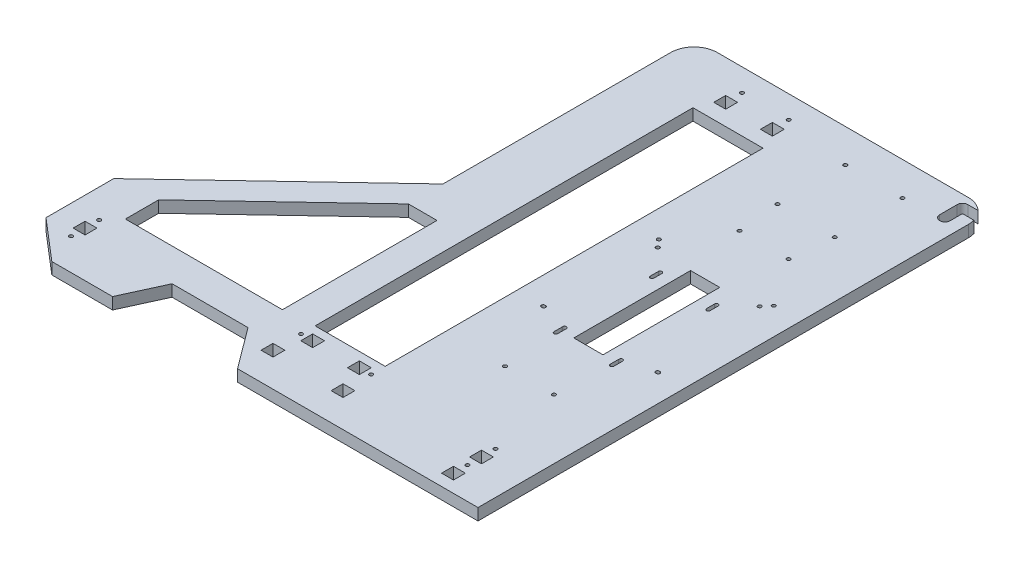
SolidWorks part; units mm, degrees
ref_plane "Front Plane" through (0, 0, 0) normal (0, 0, 1) x (1, 0, 0)
ref_plane "Top Plane" through (0, 0, 0) normal (0, 1, 0) x (1, 0, 0)
ref_plane "Right Plane" through (0, 0, 0) normal (1, 0, 0) x (0, 0, -1)
sketch "Sketch1" plane through (0, 0, 0) normal (0, 1, 0) x (1, 0, 0)
  line L0 (0, 0) -> (-235, 0)
  line L1 (-235, 0) -> (-235, -215)
  line L2 (-235, -215) -> (-380, -352)
  line L3 (-380, -352) -> (-380, -410)
  line L4 (-380, -410) -> (-345, -440)
  line L5 (-345, -440) -> (-293, -440)
  line L6 (-293, -440) -> (-277, -405)
  line L7 (-277, -405) -> (-212, -405)
  line L8 (-212, -405) -> (-185.9255, -440)
  line L9 (-185.9255, -440) -> (0, -440)
  line L10 (0, 0) -> (0, -440)
  line L12 (-293, -440) -> (-185.9255, -440) construction
  dimension "D3" = 235
  dimension "D5" = 58
  dimension "D13" = 190
  dimension "D7" = 35
  dimension "D2" = 126.686
  dimension "D11" = 65
  dimension "D15" = 52
  dimension "D12" = 30
  dimension "D10" = 35
  dimension "D14" = 16
  dimension "D6" = 380
  dimension "D4" = 440
extrude "Boss-Extrude1" add sketch "Sketch1" along normal blind 10
sketch "Sketch16" plane through (0, 10, 0) normal (0, 1, 0) x (1, 0, 0)
  line L0 (0, -440) -> (20, -440)
  line L1 (20, -440) -> (20, 0)
  line L2 (20, 0) -> (0, 0)
  line L3 (0, 0) -> (0, -440)
  dimension "D1" = 20
  dimension "D2" = 90
extrude "Boss-Extrude2" add sketch "Sketch16" against normal through all
sketch "Sketch2" plane through (0, 10, 0) normal (0, 1, 0) x (1, 0, 0)
  line L0 (-235, -215) -> (-235, -405) construction
  line L1 (-277, -405) -> (-212, -405) construction
  line L2 (-345, -440) -> (-345, -318.931) construction
  line L3 (-235, -215) -> (-380, -352) construction
  line L4 (-345, -348.5097) -> (-235, -244.5787)
  line L5 (-235, -244.5787) -> (-210.5, -244.5787)
  line L6 (-210.5, -244.5787) -> (-210.5, -377)
  line L7 (-210.5, -377) -> (-345, -377)
  line L8 (-345, -377) -> (-345, -348.5097)
  line L9 (0, -440) -> (0, 0) construction
  line L10 (-184.5, -375) -> (-124.5, -375)
  line L11 (-184.5, -375) -> (-184.5, -51.35)
  line L12 (-184.5, -51.35) -> (-124.5, -51.35)
  line L13 (-124.5, -375) -> (-124.5, -51.35)
  line L14 (-124.5, -387.1) -> (-184.5, -387.1) construction
  line L15 (-16, -440) -> (-16, 0) construction
  line L16 (20, 0) -> (-235, 0) construction
  line L17 (-355.55, -430.9571) -> (-355.55, -328.899) construction
  line L18 (-21.1, -430.1) -> (-10.9, -430.1)
  line L19 (-21.1, -430.1) -> (-21.1, -419.9)
  line L20 (-21.1, -419.9) -> (-10.9, -419.9)
  line L21 (-10.9, -430.1) -> (-10.9, -419.9)
  line L22 (-21.1, -430.1) -> (-10.9, -419.9) construction
  line L23 (-21.1, -419.9) -> (-10.9, -430.1) construction
  line L24 (-21.1, -406.1) -> (-10.9, -406.1)
  line L25 (-21.1, -406.1) -> (-21.1, -395.9)
  line L26 (-21.1, -395.9) -> (-10.9, -395.9)
  line L27 (-10.9, -406.1) -> (-10.9, -395.9)
  line L28 (-21.1, -406.1) -> (-10.9, -395.9) construction
  line L29 (-21.1, -395.9) -> (-10.9, -406.1) construction
  line L30 (-380, -410) -> (-345, -440) construction
  line L32 (-350.45, -395.9) -> (-360.65, -395.9)
  line L33 (-350.45, -395.9) -> (-350.45, -406.1)
  line L34 (-350.45, -406.1) -> (-360.65, -406.1)
  line L35 (-360.65, -395.9) -> (-360.65, -406.1)
  line L36 (-350.45, -395.9) -> (-360.65, -406.1) construction
  line L37 (-350.45, -406.1) -> (-360.65, -395.9) construction
  line L38 (-185.9255, -440) -> (20, -440) construction
  line L39 (-185.9255, -440) -> (20, -440) construction
  line L40 (-173.924, -33.35) -> (-113.924, -33.35) construction
  line L41 (-154.5, -51.35) -> (-154.5, -33.35) construction
  line L42 (-179.6, -28.25) -> (-169.4, -28.25)
  line L43 (-179.6, -28.25) -> (-179.6, -38.45)
  line L44 (-179.6, -38.45) -> (-169.4, -38.45)
  line L45 (-169.4, -28.25) -> (-169.4, -38.45)
  line L46 (-179.6, -28.25) -> (-169.4, -38.45) construction
  line L47 (-179.6, -38.45) -> (-169.4, -28.25) construction
  line L48 (-129.4, -38.45) -> (-139.6, -28.25) construction
  line L49 (-129.4, -28.25) -> (-139.6, -38.45) construction
  line L50 (-139.6, -28.25) -> (-139.6, -38.45)
  line L51 (-129.4, -38.45) -> (-139.6, -38.45)
  line L52 (-129.4, -28.25) -> (-129.4, -38.45)
  line L53 (-129.4, -28.25) -> (-139.6, -28.25)
  line L54 (-174.5, -33.35) -> (-174.5, -19.35) construction
  line L55 (-134.5, -33.35) -> (-134.5, -19.35) construction
  line L56 (-154.5, -375) -> (-154.5, -440) construction
  line L57 (-174.5, -387.1) -> (-134.5, -387.1) construction
  line L58 (-129.4, -392.2) -> (-139.6, -382) construction
  line L59 (-179.6, -382) -> (-169.4, -382)
  line L60 (-179.6, -382) -> (-179.6, -392.2)
  line L61 (-179.6, -392.2) -> (-169.4, -392.2)
  line L62 (-169.4, -382) -> (-169.4, -392.2)
  line L63 (-179.6, -382) -> (-169.4, -392.2) construction
  line L64 (-179.6, -392.2) -> (-169.4, -382) construction
  line L65 (-129.4, -382) -> (-139.6, -392.2) construction
  line L66 (-139.6, -382) -> (-139.6, -392.2)
  line L67 (-129.4, -392.2) -> (-139.6, -392.2)
  line L68 (-129.4, -382) -> (-129.4, -392.2)
  line L69 (-129.4, -382) -> (-139.6, -382)
  line L70 (-119.4, -416.2) -> (-129.6, -406) construction
  line L71 (-189.6, -406) -> (-179.4, -406)
  line L72 (-189.6, -406) -> (-189.6, -416.2)
  line L73 (-189.6, -416.2) -> (-179.4, -416.2)
  line L74 (-179.4, -406) -> (-179.4, -416.2)
  line L75 (-189.6, -406) -> (-179.4, -416.2) construction
  line L76 (-189.6, -416.2) -> (-179.4, -406) construction
  line L77 (-119.4, -406) -> (-129.6, -416.2) construction
  line L78 (-129.6, -406) -> (-129.6, -416.2)
  line L79 (-119.4, -416.2) -> (-129.6, -416.2)
  line L80 (-119.4, -406) -> (-119.4, -416.2)
  line L81 (-119.4, -406) -> (-129.6, -406)
  line L82 (-360.65, -395.9) -> (-10.9, -395.9) construction
  circle A0 centre (-16, -413) radius 1.55
  circle A1 centre (-16, -389) radius 1.55
  circle A2 centre (-355.55, -413) radius 1.55
  circle A3 centre (-355.55, -389) radius 1.55
  circle A4 centre (-174.5, -19.35) radius 1.55
  circle A5 centre (-134.5, -19.35) radius 1.55
  circle A6 centre (-124.5, -387.1) radius 1.55
  circle A7 centre (-184.5, -387.1) radius 1.55
  point P25 (-16, -425)
  point P30 (-16, -401)
  point P44 (-355.55, -401)
  point P61 (-174.5, -33.35)
  point P72 (-134.5, -33.35)
  point P85 (-174.5, -387.1)
  point P94 (-134.5, -387.1)
  point P95 (-184.5, -411.1)
  point P104 (-124.5, -411.1)
  point P105 (-154.5, -387.1)
  dimension "D13" = 3.1
  dimension "D14" = 3.1
  dimension "D23" = 3.1
  dimension "D24" = 3.1
  dimension "D31" = 3.1
  dimension "D37" = 3.1
  dimension "D1" = 21.5
  dimension "D2" = 28
  dimension "D3" = 24.5
  dimension "D4" = 60
  dimension "D7" = 26
  dimension "D8" = 10.2
  dimension "D9" = 10.2
  dimension "D10" = 10.2
  dimension "D11" = 10.2
  dimension "D12" = 24
  dimension "D15" = 24
  dimension "D19" = 10.2
  dimension "D20" = 10.2
  dimension "D26" = 12
  dimension "D27" = 10.2
  dimension "D28" = 10.2
  dimension "D33" = 10.2
  dimension "D38" = 10.2
  dimension "D39" = 10.2
  dimension "D41" = 24
  dimension "D34" = 30
  dimension "D36" = 12.1
  dimension "D30" = 18
  dimension "D29" = 40
  dimension "D17" = 15
  dimension "D32" = 14
  dimension "D35" = 20
  dimension "D16" = 12
  dimension "D21" = 90
  dimension "D25" = 24
  dimension "D5" = 353.75
  dimension "D22" = 349.75
  dimension "D40" = 30
  dimension "D6" = 65
  dimension "D42" = 0
  dimension "D43" = 0
  dimension "D18" = 16
extrude "Cut-Extrude1" cut sketch "Sketch2" against normal through all
fillet "Fillet1" radius 20 2 edges at (-235, 5, 0) (20, 5, 0)
sketch "Sketch11" [suppressed] plane through (0, 10, 0) normal (0, 1, 0) x (1, 0, 0)
  line L0 (-124.5, -213.175) -> (20, -213.175) construction
  line L1 (20, -440) -> (20, -20) construction
  line L3 (-52.25, -213.175) -> (-52.25, -440) construction
  line L6 (-124.5, -375) -> (-124.5, -51.35) construction
  line L8 (-185.9255, -440) -> (20, -440) construction
  circle A0 centre (-52.25, -413) radius 12.5
  circle A1 centre (-16, -413) radius 1.55 construction
  dimension "D1" = 25
  dimension "D2" = 0
  dimension "D3" = 0
extrude "WiringHole" [suppressed] cut sketch "Sketch11" against normal through all
sketch "Sketch9" [suppressed] plane through (0, 10, 0) normal (0, 1, 0) x (1, 0, 0)
  line L0 (-52.25, -400.5) -> (-52.25, 0) construction
  line L1 (0, 0) -> (-215, 0) construction
  line L2 (-124.5, -213.175) -> (20, -213.175) construction
  line L3 (-124.5, -375) -> (-124.5, -51.35) construction
  line L4 (-4.75, -124.675) -> (-4.75, -301.675) construction
  line L6 (-99.75, -124.675) -> (-4.75, -124.675) construction
  line L7 (-4.75, -301.675) -> (-99.75, -301.675) construction
  line L8 (-99.75, -301.675) -> (-99.75, -124.675) construction
  line L9 (20, -440) -> (20, -20) construction
  circle A0 centre (-52.25, -413) radius 12.5 construction
  circle A1 centre (-99.75, -124.675) radius 1.55
  circle A2 centre (-4.75, -124.675) radius 1.55
  circle A3 centre (-4.75, -301.675) radius 1.55
  circle A4 centre (-99.75, -301.675) radius 1.55
  dimension "D3" = 3.1
  dimension "D4" = 3.1
  dimension "D1" = 95
  dimension "D2" = 177
  dimension "D5" = 47.5
extrude "MountingHoles-PSU" [suppressed] cut sketch "Sketch9" against normal through all
sketch "Sketch10" plane through (0, 10, 0) normal (0, 1, 0) x (1, 0, 0)
  line L0 (-124.5, -213.175) -> (20, -213.175) construction
  line L1 (20, -440) -> (20, -20) construction
  line L2 (-64.75, -223.175) -> (-39.75, -223.175) construction
  line L3 (-52.25, -213.175) -> (-52.25, 0) construction
  line L7 (-124.5, -375) -> (-124.5, -51.35) construction
  line L8 (-64.75, -273.175) -> (-39.75, -273.175)
  line L9 (-64.75, -273.175) -> (-64.75, -173.175)
  line L10 (-64.75, -173.175) -> (-39.75, -173.175)
  line L11 (-39.75, -273.175) -> (-39.75, -173.175)
  line L12 (-64.75, -273.175) -> (-39.75, -173.175) construction
  line L13 (-64.75, -173.175) -> (-39.75, -273.175) construction
  line L15 (0, 0) -> (-215, 0) construction
  line L17 (-52.25, -213.175) -> (-52.25, -440) construction
  line L18 (-185.9255, -440) -> (20, -440) construction
  line L19 (-64.75, -213.175) -> (-39.75, -213.175) construction
  line L20 (-52.25, -273.175) -> (-52.25, -173.175) construction
  dimension "D1" = 25
  dimension "D2" = 100
  dimension "D3" = 0
  dimension "D4" = 0
  dimension "D5" = 0
  dimension "D6" = 10
extrude "WiringSlot" cut sketch "Sketch10" against normal through all
sketch "CenterLines" plane through (0, 10, 0) normal (0, 1, 0) x (1, 0, 0)
  line L0 (-52.25, -273.175) -> (-52.25, -173.175) construction
  line L1 (-64.75, -273.175) -> (-39.75, -273.175) construction
  line L2 (-39.75, -173.175) -> (-64.75, -173.175) construction
  line L3 (-64.75, -223.175) -> (-39.75, -223.175) construction
  line L4 (-64.75, -173.175) -> (-64.75, -273.175) construction
  line L5 (-39.75, -273.175) -> (-39.75, -173.175) construction
ref_plane "Plane1" through (-52.25, 0, 0) normal (1, 0, 0) x (0, 0, -1)
sketch "Sketch6" plane through (0, 10, 0) normal (0, 1, 0) x (1, 0, 0)
  line L0 (-52.25, -273.175) -> (-52.25, -173.175) construction
  line L1 (-76.35, -232.025) -> (-28.15, -232.025) construction
  line L2 (-28.15, -187.575) -> (-28.15, -270.075) construction
  line L3 (-64.75, -273.175) -> (-39.75, -273.175) construction
  line L4 (-64.75, -240.875) -> (-39.75, -240.875) construction
  line L5 (-39.75, -173.175) -> (-64.75, -173.175) construction
  line L6 (-28.15, -187.575) -> (-28.15, -194.575) construction
  line L7 (-26.6, -187.575) -> (-26.6, -194.575)
  line L8 (-29.7, -187.575) -> (-29.7, -194.575)
  line L9 (-64.75, -223.175) -> (-39.75, -223.175) construction
  line L10 (-64.75, -173.175) -> (-64.75, -273.175) construction
  line L11 (-39.75, -273.175) -> (-39.75, -173.175) construction
  line L12 (-28.15, -277.075) -> (-28.15, -270.075) construction
  line L13 (-29.7, -277.075) -> (-29.7, -270.075)
  line L14 (-76.35, -269.475) -> (-76.35, -194.575) construction
  line L15 (-28.15, -277.075) -> (-28.15, -194.575) construction
  line L16 (-26.6, -277.075) -> (-26.6, -270.075)
  arc A2 (-26.6, -187.575) -> (-29.7, -187.575) centre (-28.15, -187.575) ccw
  arc A3 (-29.7, -194.575) -> (-26.6, -194.575) centre (-28.15, -194.575) ccw
  circle A4 centre (-76.35, -269.475) radius 1.55
  circle A6 centre (-76.35, -194.575) radius 1.55
  arc A8 (-29.7, -277.075) -> (-26.6, -277.075) centre (-28.15, -277.075) ccw
  arc A9 (-26.6, -270.075) -> (-29.7, -270.075) centre (-28.15, -270.075) ccw
  point P20 (-28.15, -191.075)
  point P25 (-28.15, -273.575)
  dimension "D8" = 3.1
  dimension "D12" = 3.1
  dimension "D4" = 1.55
  dimension "D5" = 1.55
  dimension "D11" = 82.5
  dimension "D14" = 74.9
  dimension "D2" = 24.1
  dimension "D3" = 48.2
  dimension "D6" = 8.85
  dimension "D9" = 7
  dimension "D10" = 7
extrude "MountingHoles-RAMPS" cut sketch "Sketch6" against normal through all
mirror "Mirror1" about plane through (-52.25, 0, 0) normal (1, 0, 0) of "MountingHoles-RAMPS"
sketch "Sketch5" plane through (0, 10, 0) normal (0, 1, 0) x (1, 0, 0)
  line L0 (-39.75, -223.175) -> (-64.75, -223.175) construction
  line L3 (-39.75, -273.175) -> (-39.75, -173.175) construction
  line L5 (-64.75, -173.175) -> (-64.75, -273.175) construction
  line L7 (-31.25, -122.675) -> (-73.25, -122.675) construction
  line L8 (-31.25, -323.675) -> (-73.25, -323.675) construction
  line L9 (-52.25, -223.175) -> (-52.25, -122.675) construction
  line L10 (-52.25, -223.175) -> (-52.25, -323.675) construction
  circle A0 centre (-73.25, -122.675) radius 1.55
  circle A1 centre (-31.25, -122.675) radius 1.55
  circle A2 centre (-31.25, -323.675) radius 1.55
  circle A3 centre (-73.25, -323.675) radius 1.55
  point P17 (-52.25, -122.675)
  point P22 (-52.25, -323.675)
  dimension "D2" = 3.1
  dimension "D5" = 3.1
  dimension "D6" = 3.1
  dimension "D7" = 3.1
  dimension "D3" = 201
  dimension "D4" = 100.5
  dimension "D8" = 21
  dimension "D9" = 21
  dimension "D10" = 100.5
extrude "MountingHoles-Melzi" cut sketch "Sketch5" against normal through all
sketch "Sketch13" plane through (0, 0, 0) normal (0, -1, 0) x (-1, 0, 0)
  line L0 (64.75, -213.175) -> (124.5, -213.175) construction
  line L1 (124.5, -375) -> (124.5, -51.35) construction
  line L2 (101.46, -262.69) -> (101.46, -163.66) construction
  line L3 (52.25, -273.175) -> (52.25, -173.175) construction
  line L4 (64.75, -173.175) -> (64.75, -273.175) construction
  line L6 (101.46, -262.69) -> (3.56, -262.69) construction
  circle A0 centre (101.46, -163.66) radius 1.55
  circle A1 centre (101.46, -262.69) radius 1.55
  circle A2 centre (8.62, -170.14) radius 1.55
  circle A3 centre (3.56, -262.69) radius 1.55
  point P11 (101.46, -213.175)
  dimension "D8" = 3.1
  dimension "D6" = 3.1
  dimension "D1" = 3.1
  dimension "D2" = 49.515
  dimension "D3" = 49.21
  dimension "D4" = 6.48
  dimension "D5" = 92.84
  dimension "D7" = 97.9
extrude "Mountingholes-Smoothieboard" cut sketch "Sketch13" against normal through all
mirror "Flipped" about plane through (-52.25, 0, 0) normal (1, 0, 0) of "Mountingholes-Smoothieboard"
sketch "Sketch21" plane through (0, 10, 0) normal (0, 1, 0) x (1, 0, 0)
  line L0 (-52.25, -173.175) -> (-52.25, 0) construction
  line L1 (-39.75, -173.175) -> (-64.75, -173.175) construction
  line L2 (0, 0) -> (-215, 0) construction
  line L3 (-52.25, -57.675) -> (-23.3697, -57.675) construction
  circle A0 centre (-27.75, -28.675) radius 1.55
  circle A1 centre (-76.75, -28.675) radius 1.55
  circle A2 centre (-76.75, -86.675) radius 1.55
  circle A3 centre (-27.75, -86.675) radius 1.55
  circle A4 centre (-31.25, -122.675) radius 1.55 construction
  dimension "D1" = 3.1
  dimension "D2" = 24.5
  dimension "D3" = 29
  dimension "D4" = 65
extrude "Pi" cut sketch "Sketch21" against normal through all
sketch "Sketch17" plane through (0, 10, 0) normal (0, 1, 0) x (1, 0, 0)
  line L0 (0, 0) -> (20, 0) construction
  line L1 (20, -23.6361) -> (20, 0) construction
  line L2 (20, -440) -> (20, -20) construction
  line L3 (20, -10) -> (5, -10) construction
  line L4 (20, -14.5) -> (5, -14.5)
  line L5 (20, -5.5) -> (5, -5.5)
  arc A0 (20, -14.5) -> (20, -5.5) centre (20, -10) ccw
  arc A1 (5, -5.5) -> (5, -14.5) centre (5, -10) ccw
  point P8 (12.5, -10)
  dimension "D1" = 9
  dimension "D2" = 15
  dimension "D3" = 10
extrude "Cut-Extrude3" cut sketch "Sketch17" against normal through all
sketch "Sketch18" plane through (0, 10, 0) normal (0, 1, 0) x (1, 0, 0)
  line L0 (5, -5.5) -> (5, -14.5) construction
  line L1 (0.5, -10) -> (5, -10) construction
  line L2 (5, -10) -> (5, -25) construction
  line L3 (9.5, -10) -> (9.5, -25)
  line L4 (0.5, -10) -> (0.5, -25)
  arc A0 (5, -5.5) -> (5, -14.5) centre (5, -10) ccw construction
  arc A1 (9.5, -10) -> (0.5, -10) centre (5, -10) ccw
  arc A2 (0.5, -25) -> (9.5, -25) centre (5, -25) ccw
  point P10 (5, -17.5)
  dimension "D1" = 9
  dimension "D2" = 0
  dimension "D3" = 15
extrude "Cut-Extrude4" cut sketch "Sketch18" against normal through all
sketch "Sketch19" plane through (0, 10, 0) normal (0, 1, 0) x (1, 0, 0)
  line L0 (-5, -25) -> (15, -25) construction
  line L1 (5, -25) -> (5, -5.5) construction
  circle A0 centre (15, -25) radius 1.55
  arc A1 (5, -5.5) -> (0.5, -10) centre (5, -10) ccw construction
  circle A2 centre (-5, -25) radius 1.55
  dimension "D2" = 3.1
extrude "Cut-Extrude5" [suppressed] cut sketch "Sketch19" against normal through all
equation "\"Y-ROD-SPACING\"=75"
equation "\"Y-BED-OFFSET\"=2"
equation "\"Y-BED-ROD-INSET\"=3.5"
equation "\"T-SLOT-NUT-FILLET-RADIUS\"=0.25"
equation "\"T-SLOT-SCREW-SHAFT-RADIUS\"=1.75"
equation "\"T-SLOT-SCREW-SHAFT-CUTOUT-LENGTH\"=10.5"
equation "\"T-SLOT-NUT-DEPTH\"=4.2"
equation "\"T-SLOT-NUT-WIDTH\"=3"
equation "\"T-SLOT-NUT-END-DISTANCE\"=8"
equation "\"ACRYLIC-TAB-CUTOUT-SIZE\"=\"ACRYLIC-THICKNESS\"+\"ACRYLIC-TAB-TOLERANCE\"*2"
equation "\"ACRYLIC-TAB-WIDTH\"=\"ACRYLIC-THICKNESS\""
equation "\"ACRYLIC-M3-HOLE\"=3.1"
equation "\"SMOOTHROD-CAP-SCREW-DISTANCE\"=20"
equation "\"FRAME-WIDTH-INNER\"=370"
equation "\"D24@Sketch2\"=\"ACRYLIC-M3-HOLE\""
equation "\"D23@Sketch2\"=\"ACRYLIC-M3-HOLE\""
equation "\"D19@Sketch2\"=\"ACRYLIC-THICKNESS\"+\"ACRYLIC-TAB-TOLERANCE\"*2"
equation "\"D20@Sketch2\"=\"ACRYLIC-TAB-WIDTH\"+\"ACRYLIC-TAB-TOLERANCE\"*2"
equation "\"D37@Sketch2\"=\"ACRYLIC-M3-HOLE\""
equation "\"D33@Sketch2\"=\"ACRYLIC-TAB-CUTOUT-SIZE\""
equation "\"D38@Sketch2\"=\"ACRYLIC-TAB-CUTOUT-SIZE\""
equation "\"D39@Sketch2\"=\"ACRYLIC-TAB-CUTOUT-SIZE\""
equation "\"D13@Sketch2\"=\"ACRYLIC-M3-HOLE\""
equation "\"D14@Sketch2\"=\"ACRYLIC-M3-HOLE\""
equation "\"D8@Sketch2\"=\"ACRYLIC-TAB-CUTOUT-SIZE\""
equation "\"D9@Sketch2\"=\"ACRYLIC-TAB-CUTOUT-SIZE\""
equation "\"D10@Sketch2\"=\"ACRYLIC-TAB-CUTOUT-SIZE\""
equation "\"D11@Sketch2\"=\"ACRYLIC-TAB-CUTOUT-SIZE\""
equation "\"D31@Sketch2\"=\"ACRYLIC-M3-HOLE\""
equation "\"D27@Sketch2\"=\"ACRYLIC-THICKNESS\"+\"ACRYLIC-TAB-TOLERANCE\"*2"
equation "\"D28@Sketch2\"=\"ACRYLIC-TAB-WIDTH\"+\"ACRYLIC-TAB-TOLERANCE\"*2"
equation "\"NEMA17-HOLE-SPACING\"=31"
equation "\"NEMA17-CENTRAL-CUTOUT\"=22.5"
equation "\"Z-BRACKET-REACH\"=55"
equation "\"TOP-BRACKET-SPACING\"=40"
equation "\"D29@Sketch2\"=\"TOP-BRACKET-SPACING\""
equation "\"ACRYLIC-THICKNESS\"=10"
equation "\"SMOOTHROD-Z-LENGTH\"=350"
equation "\"D5@Sketch2\"=\"SMOOTHROD-Z-LENGTH\"-\"SMOOTHROD-TIGHTENING-HEADROOM\"+4"
equation "\"SMOOTHROD-X-LENGTH\"=350"
equation "\"SMOOTHROD-Y-LENGTH\"=350"
equation "\"D22@Sketch2\"=\"SMOOTHROD-Y-LENGTH\"-\"SMOOTHROD-TIGHTENING-HEADROOM\""
equation "\"SMOOTHROD-TIGHTENING-HEADROOM\"=.25"
equation "\"X-ROD-SPACING\"=45"
equation "\"Z-ROD-SPACING\"=17.5"
equation "\"LEADSCREW-Z-LENGTH\"=300"
equation "\"SCREW-HEAD-RADIUS\"=6"
equation "\"PRINTED-X-SMOOTHROD-DIAMETER\"=8.2"
equation "\"PRINTED-X-SMOOTHROD-CUTOUT\"=10"
equation "\"PRINTED-X-BASE-HEIGHT\"=10"
equation "\"PRINTED-LM8UU-CUTOUT-SIZE\"=15.25"
equation "\"PRINTED-LM8UU-CUTOUT-LENGTH\"=24.5"
equation "\"PRINTED-X-IDLER-HEIGHT\"=16"
equation "\"PSU-MOUNTING-WIDTH\"=95"
equation "\"PSU-MOUNTING-HEIGHT\"=177"
equation "\"D1@Sketch9\"=\"PSU-MOUNTING-WIDTH\""
equation "\"D3@Sketch9\"=\"ACRYLIC-M3-HOLE\""
equation "\"D1@Boss-Extrude1\"=\"ACRYLIC-THICKNESS\""
equation "\"D6@Sketch1\"=\"SMOOTHROD-Y-LENGTH\"+30"
equation "\"D4@Sketch9\"=\"ACRYLIC-M3-HOLE\""
equation "\"D2@Sketch9\"=\"PSU-MOUNTING-HEIGHT\""
equation "\"D5@Sketch9\"=\"PSU-MOUNTING-WIDTH\"/2"
equation "\"D4@Sketch1\"=\"SMOOTHROD-Z-LENGTH\"+90"
equation "\"D8@Sketch6\"=\"ACRYLIC-M3-HOLE\""
equation "\"D12@Sketch6\"=\"ACRYLIC-M3-HOLE\""
equation "\"D2@Sketch5\"=\"ACRYLIC-M3-HOLE\""
equation "\"D5@Sketch5\"=\"ACRYLIC-M3-HOLE\""
equation "\"D6@Sketch5\"=\"ACRYLIC-M3-HOLE\""
equation "\"D7@Sketch5\"=\"ACRYLIC-M3-HOLE\""
equation "\"D1@Sketch13\"=\"ACRYLIC-M3-HOLE\""
equation "\"D6@Sketch13\"=\"ACRYLIC-M3-HOLE\""
equation "\"D8@Sketch13\"=\"ACRYLIC-M3-HOLE\""
equation "\"D4@Sketch6\"=\"ACRYLIC-M3-HOLE\"/2"
equation "\"D5@Sketch6\"=\"ACRYLIC-M3-HOLE\"/2"
equation "\"Y-BED-SCREW-SPACING\"=209"
equation "\"Y-BED-SCREW-CUTOUT-SLOT-HEIGHT\"=2"
equation "\"ACRYLIC-THICKNESS2\"=4.5"
equation "\"ACRYLIC-TAB-TOLERANCE\"=.1"
equation "\"Z-ROD-INSET\"=16"
equation "\"SCREW-LENGTH-FRAME\"=\"ACRYLIC-THICKNESS\" + 10"
equation "\"SCREW-LENGTH-MOTOR\"=\"ACRYLIC-THICKNESS\" + 5"
equation "\"SCREW-LENGTH-EXTRUDER\"=28"
equation "\"Y-BELT-TO-ROD-DISTANCE\"=20"
equation "\"SPOOL-HOLDER-ROD-SPACING\"=150"
equation "\"ACRYLIC-X-CARRIAGE-WIDTH\"=55"
equation "\"ACRYLIC-X-CARRIAGE-HEIGHT\"=75"
equation "\"ACRYLIC-X-CARRIAGE-LM8UU-CUTOUT-WIDTH\"=24.25"
equation "\"ACRYLIC-X-CARRIAGE-SCREW-SPACING-X\"=15"
equation "\"ACRYLIC-X-CARRIAGE-SCREW-SPACING-Y\"=33"
equation "\"ACRYLIC-X-CARRIAGE-CENTER-TAB-SPACING\"=14"
equation "\"ACRYLIC-X-CARRIAGE-EXTRUDER-OFFSET\"=26"
equation "\"ACRYLIC-X-CARRIAGE-EXTRUDER-ANGLE\"=90"
equation "\"ACRYLIC-X-CARRIAGE-EXTRUDER-SHELF-DEPTH\"=\"ACRYLIC-X-CARRIAGE-EXTRUDER-OFFSET\" + 28"
equation "\"ACRYLIC-X-CARRIAGE-EXTRUDER-BRACE-SPACING\"=23"
equation "\"ACRYLIC-X-CARRIAGE-EXTRUDER-BRACE-TAB-OFFSET\"=20"
equation "\"ACRYLIC-X-CARRIAGE-EXTRUDER-BRACE-HEIGHT\"=35"
equation "\"ACRYLIC-X-CARRIAGE-EXTRUDER-BRACE-SCREW-SPACING\"=22"
equation "\"D1@Sketch19\"=\"SMOOTHROD-CAP-SCREW-DISTANCE\"/2"
equation "\"D2@Sketch19\"=\"ACRYLIC-M3-HOLE\""
equation "\"D1@Sketch21\"=\"ACRYLIC-M3-HOLE\""
